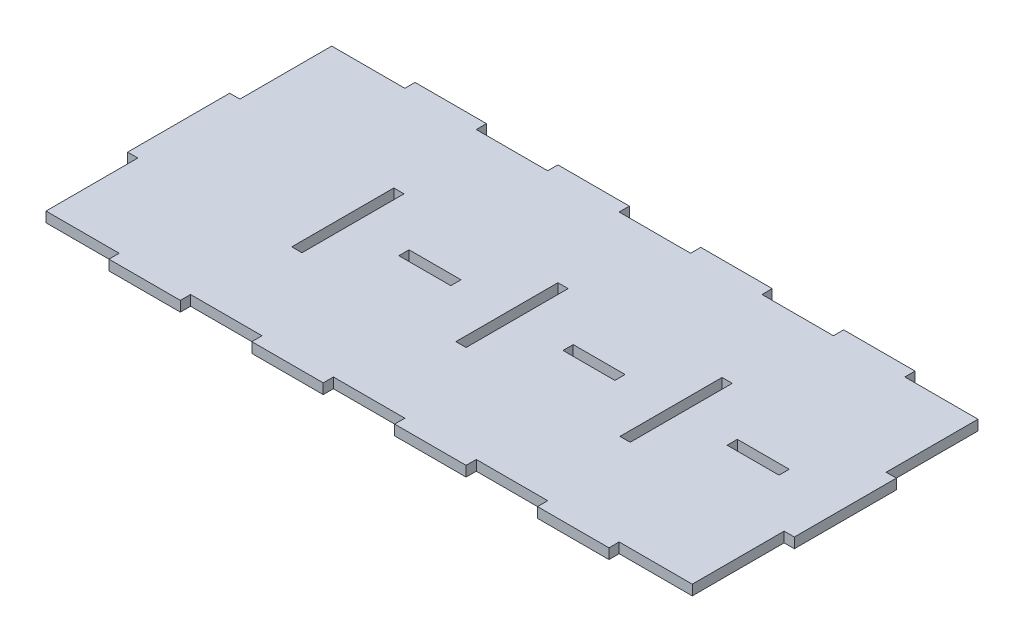
SolidWorks part; units mm, degrees
ref_plane "Front Plane" through (0, 0, 0) normal (0, 0, 1) x (1, 0, 0)
ref_plane "Top Plane" through (0, 0, 0) normal (0, 1, 0) x (1, 0, 0)
ref_plane "Right Plane" through (0, 0, 0) normal (1, 0, 0) x (0, 0, -1)
sketch "Sketch1" plane through (0, 0, 0) normal (0, 1, 0) x (1, 0, 0)
  line L0 (-98, 15) -> (-95, 15)
  line L1 (-98, -45) -> (98, -45)
  line L2 (-98, -45) -> (-98, 45)
  line L3 (-98, 45) -> (98, 45)
  line L4 (98, -45) -> (98, 45)
  line L5 (-98, -45) -> (98, 45) construction
  line L6 (-98, 45) -> (98, -45) construction
  line L7 (-95, 15) -> (-95, 45)
  line L8 (-98, -15) -> (-95, -15)
  line L9 (-95, -15) -> (-95, -45)
  line L10 (95, 45) -> (95, 15)
  line L11 (95, 15) -> (98, 15)
  line L12 (98, -15) -> (95, -15)
  line L13 (95, -15) -> (95, -45)
  line L14 (-98, -42) -> (-73.5, -42)
  line L15 (-73.5, -42) -> (-73.5, -45)
  line L16 (-73.5, -45) -> (-52.5, -45)
  line L17 (-52.5, -45) -> (-52.5, -42)
  line L18 (-52.5, -42) -> (-31.5, -42)
  line L19 (-31.5, -42) -> (-31.5, -45)
  line L20 (-31.5, -45) -> (-10.5, -45)
  line L21 (-10.5, -45) -> (-10.5, -42)
  line L22 (-10.5, -42) -> (10.5, -42)
  line L23 (10.5, -42) -> (10.5, -45)
  line L24 (10.5, -45) -> (31.5, -45)
  line L25 (31.5, -45) -> (31.5, -42)
  line L26 (31.5, -42) -> (52.5, -42)
  line L27 (52.5, -42) -> (52.5, -45)
  line L28 (52.5, -45) -> (73.5, -45)
  line L29 (73.5, -45) -> (73.5, -42)
  line L30 (73.5, -42) -> (98, -42)
  line L31 (-98, 42) -> (-73.5, 42)
  line L32 (-73.5, 42) -> (-73.5, 45)
  line L33 (-73.5, 45) -> (-52.5, 45)
  line L34 (-52.5, 45) -> (-52.5, 42)
  line L35 (-52.5, 42) -> (-31.5, 42)
  line L36 (-31.5, 42) -> (-31.5, 45)
  line L37 (-31.5, 45) -> (-10.5, 45)
  line L38 (-10.5, 45) -> (-10.5, 42)
  line L39 (-10.5, 42) -> (10.5, 42)
  line L40 (10.5, 42) -> (10.5, 45)
  line L41 (10.5, 45) -> (31.5, 45)
  line L42 (31.5, 45) -> (31.5, 42)
  line L43 (31.5, 42) -> (52.5, 42)
  line L44 (52.5, 42) -> (52.5, 45)
  line L45 (52.5, 45) -> (73.5, 45)
  line L46 (73.5, 45) -> (73.5, 42)
  line L47 (73.5, 42) -> (98, 42)
  line L49 (-49.75, -15) -> (-46.75, -15)
  line L50 (-49.75, -15) -> (-49.75, 15)
  line L51 (-49.75, 15) -> (-46.75, 15)
  line L52 (-46.75, -15) -> (-46.75, 15)
  line L53 (-49.75, -15) -> (-46.75, 15) construction
  line L54 (-49.75, 15) -> (-46.75, -15) construction
  line L55 (-1.5, -15) -> (1.5, -15)
  line L56 (-1.5, -15) -> (-1.5, 15)
  line L57 (-1.5, 15) -> (1.5, 15)
  line L58 (1.5, -15) -> (1.5, 15)
  line L59 (-1.5, -15) -> (1.5, 15) construction
  line L60 (-1.5, 15) -> (1.5, -15) construction
  line L61 (46.75, -15) -> (49.75, -15)
  line L62 (46.75, -15) -> (46.75, 15)
  line L63 (46.75, 15) -> (49.75, 15)
  line L64 (49.75, -15) -> (49.75, 15)
  line L65 (46.75, -15) -> (49.75, 15) construction
  line L66 (46.75, 15) -> (49.75, -15) construction
  line L67 (64.75, -1.5) -> (80, -1.5)
  line L68 (64.75, -1.5) -> (64.75, 1.5)
  line L69 (64.75, 1.5) -> (80, 1.5)
  line L70 (80, -1.5) -> (80, 1.5)
  line L71 (64.75, -1.5) -> (80, 1.5) construction
  line L72 (64.75, 1.5) -> (80, -1.5) construction
  line L73 (16.5, -1.5) -> (31.75, -1.5)
  line L74 (16.5, -1.5) -> (16.5, 1.5)
  line L75 (16.5, 1.5) -> (31.75, 1.5)
  line L76 (31.75, -1.5) -> (31.75, 1.5)
  line L77 (16.5, -1.5) -> (31.75, 1.5) construction
  line L78 (16.5, 1.5) -> (31.75, -1.5) construction
  line L79 (-31.75, -1.5) -> (-16.5, -1.5)
  line L80 (-31.75, -1.5) -> (-31.75, 1.5)
  line L81 (-31.75, 1.5) -> (-16.5, 1.5)
  line L82 (-16.5, -1.5) -> (-16.5, 1.5)
  line L83 (-31.75, -1.5) -> (-16.5, 1.5) construction
  line L84 (-31.75, 1.5) -> (-16.5, -1.5) construction
  point P0 (0, 0)
  point P38 (-48.25, 0)
  point P59 (0, 0)
  point P64 (48.25, 0)
  point P69 (72.375, 0)
  point P74 (24.125, 0)
  point P79 (-24.125, 0)
  dimension "D1" = 196
  dimension "D2" = 90
  dimension "D3" = 30
  dimension "D4" = 30
  dimension "D5" = 30
  dimension "D6" = 3
  dimension "D7" = 3
  dimension "D8" = 3
  dimension "D9" = 3
  dimension "D10" = 24.5
  dimension "D11" = 21
  dimension "D12" = 21
  dimension "D13" = 21
  dimension "D14" = 21
  dimension "D15" = 21
  dimension "D16" = 21
  dimension "D17" = 21
  dimension "D18" = 3
  dimension "D19" = 3
  dimension "D20" = 3
  dimension "D21" = 3
  dimension "D22" = 3
  dimension "D23" = 3
  dimension "D24" = 3
  dimension "D25" = 3
  dimension "D26" = 3
  dimension "D27" = 3
  dimension "D28" = 3
  dimension "D29" = 3
  dimension "D30" = 3
  dimension "D31" = 146.25
  dimension "D32" = 49.75
  dimension "D33" = 15.25
  dimension "D34" = 15.25
  dimension "D35" = 15.25
  dimension "D36" = 25.625
  dimension "D37" = 73.875
  dimension "D38" = 122.125
  dimension "D39" = 3
  dimension "D40" = 3
  dimension "D41" = 3
  dimension "D42" = 30
  dimension "D43" = 30
  dimension "D44" = 30
extrude "Boss-Extrude1" add sketch "Sketch1" along normal blind 3 contours L13 L12 L4 L11 L10 L3 L7 L0 L2 L8 L9 L1 region at (-96.5, 0, -12.8432)
